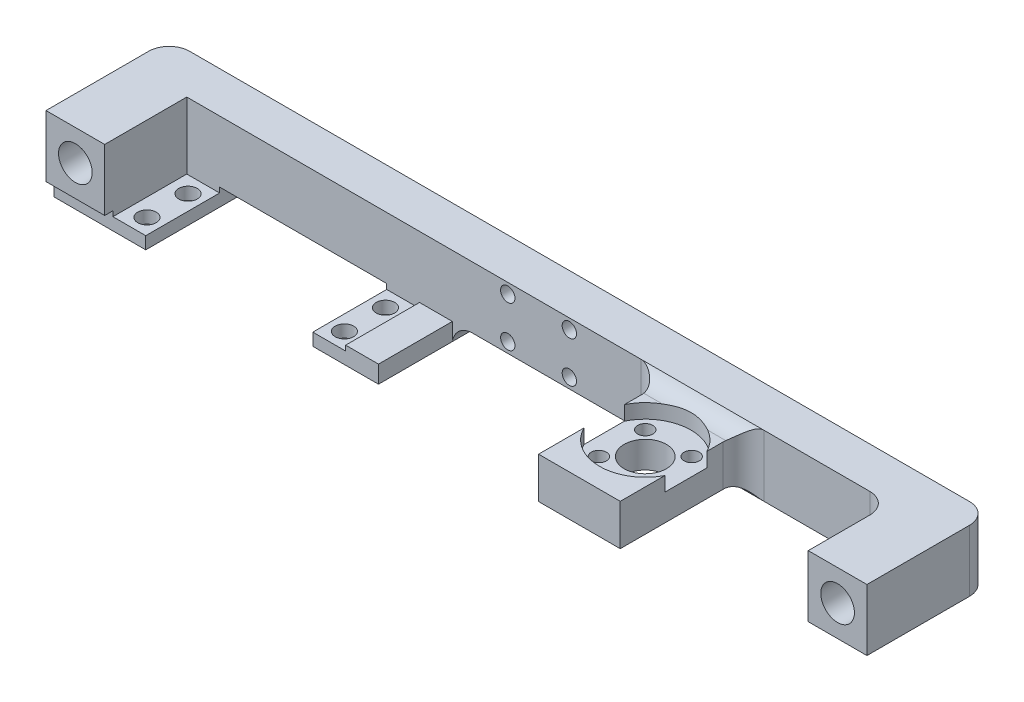
SolidWorks part; units mm, degrees
ref_plane "Plan de face" through (0, 0, 0) normal (0, 0, 1) x (1, 0, 0)
ref_plane "Plan de dessus" through (0, 0, 0) normal (0, 1, 0) x (1, 0, 0)
ref_plane "Plan de droite" through (0, 0, 0) normal (1, 0, 0) x (0, 0, -1)
sketch "Esquisse1" plane through (0, 0, 0) normal (0, 0, 1) x (1, 0, 0)
  line L6 (-92.85, 0) -> (92.85, 0) construction
  line L7 (100, -7.5) -> (-100, -7.5)
  line L18 (100, -7.5) -> (100, 7.5)
  line L19 (100, 7.5) -> (-100, 7.5)
  line L20 (-100, -7.5) -> (-100, 7.5)
  line L21 (100, -7.5) -> (-100, 7.5) construction
  line L22 (100, 7.5) -> (-100, -7.5) construction
  circle A0 centre (-92.85, 0) radius 4.1
  circle A5 centre (92.85, 0) radius 4.1
  point P0 (0, 0)
  dimension "D3" = 8.2
  dimension "D5" = 185.7
  dimension "D15" = 8.2
  dimension "D2" = 15
  dimension "D4" = 200
extrude "Boss.-Extru.1" add sketch "Esquisse1" against normal blind 10
sketch "Esquisse11" plane through (0, 0, 0) normal (0, 0, -1) x (-1, 0, 0)
  line L1 (85.7, -7.5) -> (100, -7.5)
  line L2 (85.7, -7.5) -> (85.7, 7.5)
  line L3 (85.7, 7.5) -> (100, 7.5)
  line L4 (100, -7.5) -> (100, 7.5)
  line L5 (85.7, -7.5) -> (100, 7.5) construction
  line L6 (85.7, 7.5) -> (100, -7.5) construction
  circle A0 centre (92.85, 0) radius 4.1 construction
  circle A1 centre (92.85, 0) radius 4.1
extrude "Boss.-Extru.4" add sketch "Esquisse11" against normal blind 20
mirror "Symétrie1" about plane through (0, 0, 0) normal (1, 0, 0) of "Boss.-Extru.4"
sketch "Esquisse12" plane through (0, 0, 0) normal (0, 0, 1) x (1, 0, 0)
  line L0 (-85.7, 7.5) -> (-85.7, -7.5) construction
  line L1 (-85.7, -8.75) -> (-77.7, -8.75)
  line L4 (-77.7, -8.75) -> (-77.7, -11.75)
  line L5 (-77.7, -11.75) -> (-100, -11.75)
  line L6 (-100, -11.75) -> (-100, -7.5)
  line L7 (-100, -7.5) -> (-85.7, -7.5)
  line L8 (-85.7, 7.5) -> (-85.7, -7.5) construction
  line L9 (-85.7, -7.5) -> (-85.7, -8.75)
  line L18 (-37, -8.75) -> (-29, -8.75)
  line L19 (-37, -8.75) -> (-37, -11.75)
  line L20 (-37, -11.75) -> (-21, -11.75)
  line L22 (-21, -11.75) -> (-21, -7.5)
  line L23 (-85.7, -7.5) -> (85.7, -7.5) construction
  line L24 (-21, -7.5) -> (-29, -7.5)
  line L25 (-29, -7.5) -> (-29, -8.75)
  circle A0 centre (-92.85, 0) radius 4.1 construction
  point P22 (-22.0348, -11.75)
  dimension "D1" = 3
  dimension "D2" = 8
  dimension "D3" = 8.75
  dimension "D4" = 3
  dimension "D5" = 8
  dimension "D6" = 40.7
  dimension "D7" = 8
extrude "Boss.-Extru.5" add sketch "Esquisse12" along normal blind 18 separate body
sketch "Esquisse17" plane through (0, 0, 0) normal (0, 0, -1) x (-1, 0, 0)
  line L0 (100, -7.5) -> (-100, -7.5) construction
  line L3 (85.7, -7.5) -> (77.7, -7.5)
  line L4 (77.7, -8.75) -> (77.7, -7.5)
  line L6 (85.7, -7.5) -> (85.7, -8.75)
  line L7 (85.7, -8.75) -> (77.7, -8.75)
  line L8 (77.7, -8.75) -> (77.7, -11.75)
  line L9 (77.7, -11.75) -> (100, -11.75)
  line L10 (100, -11.75) -> (100, -7.5)
  line L11 (100, -7.5) -> (85.7, -7.5)
  line L14 (77.7, -8.75) -> (77.7, -11.75)
  line L15 (77.7, -11.75) -> (100, -11.75)
  line L16 (100, -11.75) -> (100, -7.5)
  line L17 (100, -7.5) -> (85.7, -7.5)
  line L24 (37, -8.75) -> (37, -7.5)
  line L25 (37, -7.5) -> (29, -7.5)
  line L30 (37, -11.75) -> (37, -8.75)
  line L31 (37, -8.75) -> (29, -8.75)
  line L32 (29, -8.75) -> (29, -7.5)
  line L33 (29, -7.5) -> (21, -7.5)
  line L34 (21, -7.5) -> (21, -11.75)
  line L35 (21, -11.75) -> (37, -11.75)
  line L36 (37, -11.75) -> (37, -8.75)
  line L39 (29, -7.5) -> (21, -7.5)
  line L40 (21, -7.5) -> (21, -11.75)
  line L41 (21, -11.75) -> (37, -11.75)
  point P13 (0, 0)
  dimension "D2" = 0
  dimension "D1" = 0
extrude "Boss.-Extru.9" add sketch "Esquisse17" along normal up to surface (10 mm away) up to face at (96.95, 0, -10)
sketch "Esquisse18" plane through (0, -8.75, 0) normal (0, 1, 0) x (1, 0, 0)
  line L0 (-77.7, -18) -> (-77.7, 0) construction
  line L1 (-81.4, -4) -> (-81.4, -14) construction
  circle A0 centre (-81.4, -4) radius 2.25
  circle A1 centre (-81.4, -14) radius 2.25
  point P4 (-77.7, -9)
  point P7 (-81.4, -9)
  dimension "D1" = 4.5
  dimension "D2" = 4.5
  dimension "D3" = 10
  dimension "D4" = 3.7
extrude "Enlèv. mat.-Extru.1" cut sketch "Esquisse18" against normal through all
ref_plane "Plan1" through (-57.35, 0, 0) normal (-1, 0, 0) x (0, 0, 1)
mirror "Symétrie14" about plane through (-57.35, 0, 0) normal (-1, 0, 0) of "Enlèv. mat.-Extru.1"
sketch "Esquisse19" plane through (0, 0, 0) normal (0, 0, 1) x (1, 0, 0)
  line L1 (7.5, -5) -> (-7.5, -5) construction
  line L2 (7.5, -5) -> (7.5, 5) construction
  line L3 (7.5, 5) -> (-7.5, 5) construction
  line L4 (-7.5, -5) -> (-7.5, 5) construction
  line L5 (7.5, -5) -> (-7.5, 5) construction
  line L6 (7.5, 5) -> (-7.5, -5) construction
  circle A0 centre (-7.5, 5) radius 1.75
  circle A1 centre (7.5, 5) radius 1.75
  circle A2 centre (7.5, -5) radius 1.75
  circle A3 centre (-7.5, -5) radius 1.75
  point P0 (0, 0)
  dimension "D3" = 3.5
  dimension "D1" = 10
  dimension "D2" = 15
extrude "Enlèv. mat.-Extru.2" cut sketch "Esquisse19" against normal through all
sketch "Esquisse20" plane through (0, 0, 0) normal (0, 1, 0) x (1, 0, 0)
  line L0 (30, 0) -> (49.9, 0)
  line L1 (30, 0) -> (30, -30)
  line L2 (49.9, 0) -> (49.9, -30)
  line L3 (30, -30) -> (49.9, -30)
  line L4 (-10.5875, 0) -> (10.5875, 0) construction
  dimension "D1" = 19.9
  dimension "D2" = 30
  dimension "D3" = 30
extrude "Boss.-Extru.10" add sketch "Esquisse20" along normal mid plane 10
sketch "Esquisse21" plane through (0, 5, 0) normal (0, 1, 0) x (1, 0, 0)
  line L0 (85.7, 0) -> (-85.7, 0) construction
  circle A0 centre (40, -14) radius 11.15
  dimension "D1" = 22.3
  dimension "D2" = 14
  dimension "D3" = 40
extrude "Enlèv. mat.-Extru.3" cut sketch "Esquisse21" against normal blind 3.5
sketch "Esquisse22" plane through (0, 1.5, 0) normal (0, 1, 0) x (1, 0, 0)
  circle A0 centre (40, -14) radius 5.15
  arc A1 (49.9, -8.8704) -> (30, -9.0682) centre (40, -14) ccw construction
  dimension "D1" = 10.3
extrude "Enlèv. mat.-Extru.4" cut sketch "Esquisse22" against normal through all
sketch "Esquisse23" plane through (0, 1.5, 0) normal (0, 1, 0) x (1, 0, 0)
  line L1 (45.6569, -19.6569) -> (34.3431, -19.6569) construction
  line L2 (45.6569, -19.6569) -> (45.6569, -8.3431) construction
  line L3 (45.6569, -8.3431) -> (34.3431, -8.3431) construction
  line L4 (34.3431, -19.6569) -> (34.3431, -8.3431) construction
  line L5 (45.6569, -19.6569) -> (34.3431, -8.3431) construction
  line L6 (45.6569, -8.3431) -> (34.3431, -19.6569) construction
  circle A0 centre (40, -14) radius 5.15 construction
  circle A1 centre (34.3431, -8.3431) radius 1.85
  circle A2 centre (45.6569, -8.3431) radius 1.85
  circle A3 centre (45.6569, -19.6569) radius 1.85
  circle A4 centre (34.3431, -19.6569) radius 1.85
  point P0 (40, -14)
  point P11 (46.0847, -8.8061)
  dimension "D2" = 3.7
  dimension "D1" = 8
extrude "Enlèv. mat.-Extru.5" cut sketch "Esquisse23" against normal through all
fillet "Congé2" radius 5 8 edges at (-21, -7.5, -5) (-100, -2.125, -10) (100, 0, -10) (85.7, 0, 0) (39.95, -5, 0) (49.9, 0, 0) (39.95, 5, 0) (30, 0, 0)
